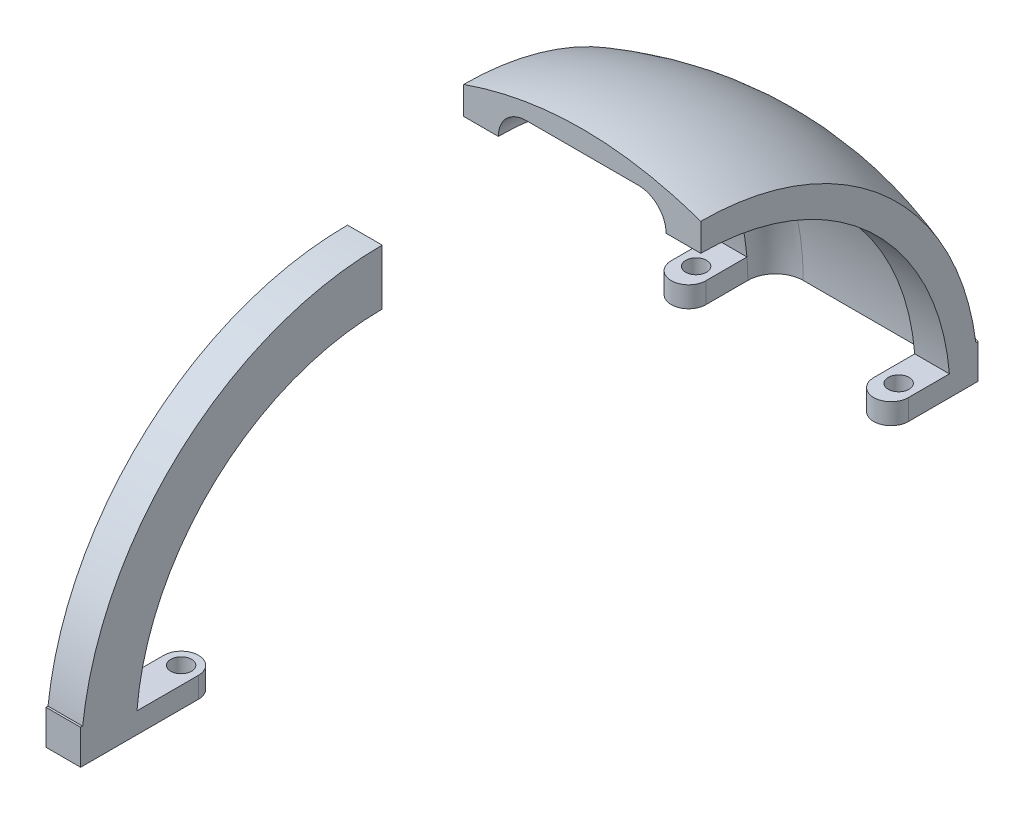
SolidWorks part; units mm, degrees
ref_plane "Front Plane" through (0, 0, 0) normal (0, 0, 1) x (1, 0, 0)
ref_plane "Top Plane" through (0, 0, 0) normal (0, 1, 0) x (1, 0, 0)
ref_plane "Right Plane" through (0, 0, 0) normal (1, 0, 0) x (0, 0, -1)
sketch "Sketch1" plane through (0, 0, 0) normal (0, 1, 0) x (1, 0, 0)
  line L0 (0, 55) -> (0, -55) construction
  line L1 (-55, 0) -> (55, 0) construction
  line L2 (-55, 20.7263) -> (-55, -21.0382) construction
  line L3 (-6.2, 54.0459) -> (10.01, 54.0459)
  line L4 (-15.2, 44) -> (-10.2, 44)
  line L5 (-15.2, 44) -> (-15.2, 54.0459)
  line L7 (-10.2, 44) -> (-10.2, 50.0459)
  line L12 (1.905, 54.0459) -> (1.905, 57.0459) construction
  line L13 (19.01, 44) -> (14.01, 44)
  line L14 (19.01, 44) -> (19.01, 54.0459)
  line L16 (14.01, 44) -> (14.01, 50.0459)
  line L17 (-10.2, 50.0459) -> (-15.2, 50.0459)
  line L22 (2.5, -41.91) -> (-2.5, -41.91)
  line L23 (2.5, -41.91) -> (2.5, -58.91)
  line L24 (2.5, -58.91) -> (-2.5, -58.91)
  line L25 (-2.5, -41.91) -> (-2.5, -58.91)
  line L26 (14.01, 50.0459) -> (19.01, 50.0459)
  line L27 (-2.5, -50.91) -> (2.5, -50.91)
  line L28 (-2.5, -15.41) -> (2.5, -15.41) construction
  circle A0 centre (0, 0) radius 55 construction
  circle A1 centre (0, -41.91) radius 1.5 construction
  circle A2 centre (16.5327, 45.0784) radius 1.5 construction
  circle A4 centre (0, -41.91) radius 1.5
  circle A8 centre (-12.7, 44) radius 2.5
  circle A9 centre (16.51, 44) radius 2.5
  circle A10 centre (0, -41.91) radius 2.5
  arc A11 (14.01, 50.0459) -> (10.01, 54.0459) centre (10.01, 50.0459) ccw
  arc A12 (-6.2, 54.0459) -> (-10.2, 50.0459) centre (-6.2, 50.0459) ccw
  circle A13 centre (0, 0) radius 50 construction
  circle A14 centre (-12.7049, 45.0912) radius 1.5 construction
  circle A15 centre (16.5327, 45.0784) radius 1.5
  circle A16 centre (-12.7049, 45.0912) radius 1.5
  spline S0 degree 2 poles (-15.2, 54.0459) (1.905, 60.0459) (19.01, 54.0459) knots 0 0 0 1 1 1
  dimension "D1" = 110
  dimension "D2" = 5
  dimension "D3" = 5
  dimension "D4" = 100
  dimension "D5" = 8
  dimension "D6" = 3
  dimension "D7" = 5
  dimension "D10" = 4
  dimension "D8" = 5
  dimension "D9" = 17
extrude "Boss-Extrude1" add sketch "Sketch1" along normal blind 3 contours A16 L4 A8 | A16 A8 L7 L17 L5 | A16 L4 A8 | A16 A8 L4 | S0 L5 L17 A12 L3 A11 L26 L14 | A15 L13 A9 | A15 L13 A9 | A15 A9 L13 | A15 A9 L14 L26 L16 | L27 L25 L24 L23 | A10 L25 L27 L23 | L22 A10 A4 | L22 A10 A4 region at (-9.2753, 0, -53.1212) region at (-12.6999, 0, -47.9735) region at (16.5098, 0, -47.9721) region at (-12.6997, 0, -42.8829) region at (-10.9002, 0, -44.8348) region at (14.7243, 0, -44.8518) region at (16.5085, 0, -42.8805) region at (-14.5064, 0, -44.8299) region at (18.3266, 0, -44.8292) region at (0, 0, 44.3541) region at (2, 0, 41.8541) region at (0, 0, 47.3696) region at (0, 0, 54.91)
extrude "Boss-Extrude2" add sketch "Sketch1<4>" along normal blind 5 contours S0 L5 L17 A12 L3 A11 L26 L14 | L27 L25 L24 L23 region at (-9.2753, 0, -53.1212) region at (0, 0, 54.91)
sketch "Sketch1<4>" plane through (0, 0, 0) normal (0, 1, 0) x (1, 0, 0) same geometry as "Sketch1"
sketch "Sketch2" plane through (0, 5, 0) normal (0, 1, 0) x (1, 0, 0)
  line L0 (14.01, 34.0459) -> (-10.2, 34.0459)
  line L5 (-15.2, 54.0459) -> (-15.2, 50.0459)
  line L6 (-15.2, 50.0459) -> (-10.2, 50.0459)
  line L7 (-6.2, 54.0459) -> (10.01, 54.0459)
  line L8 (14.01, 50.0459) -> (19.01, 50.0459)
  line L9 (19.01, 50.0459) -> (19.01, 54.0459)
  line L10 (-15.2, 54.0459) -> (-15.2, 50.0459)
  line L11 (-15.2, 50.0459) -> (-10.2, 50.0459)
  line L12 (-6.2, 54.0459) -> (10.01, 54.0459)
  line L13 (14.01, 50.0459) -> (19.01, 50.0459)
  line L14 (19.01, 50.0459) -> (19.01, 54.0459)
  arc A2 (-6.2, 54.0459) -> (-10.2, 50.0459) centre (-6.2, 50.0459) ccw
  arc A3 (14.01, 50.0459) -> (10.01, 54.0459) centre (10.01, 50.0459) ccw
  arc A4 (-6.2, 54.0459) -> (-10.2, 50.0459) centre (-6.2, 50.0459) ccw
  arc A5 (14.01, 50.0459) -> (10.01, 54.0459) centre (10.01, 50.0459) ccw
  parabola Q1 (19.01, 54.0459) -> (-15.2, 54.0459) focus (1.905, 32.6642) apex (1.905, 57.0459)
  parabola Q2 (19.01, 54.0459) -> (-15.2, 54.0459) focus (1.905, 32.6642) apex (1.905, 57.0459)
  dimension "D2" = 20
  dimension "D1" = 0
sketch "Sketch3" plane through (19.01, 0, 0) normal (1, 0, 0) x (0, 0, -1)
  line L6 (54.0459, 0) -> (54.0459, 5)
  line L7 (54.0459, 5) -> (50.0459, 5)
  line L8 (54.0459, 5) -> (50.0459, 5)
  line L9 (50.0459, 3) -> (44, 3)
  line L10 (44, 3) -> (44, 0)
  line L11 (44, 0) -> (54.0459, 0)
  line L12 (54.0459, 0) -> (54.0459, 5)
  line L15 (50.0459, 3) -> (44, 3)
  line L16 (44, 3) -> (44, 0)
  line L17 (44, 0) -> (54.0459, 0)
  line L18 (50.0459, 5) -> (50.0459, 3)
  line L19 (50.0459, 5) -> (50.0459, 3)
  circle A0 centre (-2, -5) radius 60 construction
  circle A1 centre (-2, -5) radius 50 construction
  point P7 (27.9809, 0)
  dimension "D1" = 0
  dimension "D3" = 100
  dimension "D4" = 120
  dimension "D2" = 46
  dimension "D5" = 5
sketch "Sketch6" plane through (0, 0, 0) normal (0, -1, 0) x (1, 0, 0)
  line L0 (-6.2, -14.0459) -> (10.01, -14.0459)
  line L1 (-15.2, -50.0459) -> (-10.2, -50.0459) construction
  line L2 (19.01, -50.0459) -> (14.01, -50.0459) construction
  line L3 (-15.2, -50.0459) -> (-10.2, -50.0459)
  line L4 (19.01, -50.0459) -> (14.01, -50.0459)
  line L5 (-15.2, -44) -> (-15.2, -54.0459)
  line L6 (19.01, -54.0459) -> (19.01, -44)
  line L7 (14.01, -44) -> (14.01, -50.0459)
  line L8 (10.01, -54.0459) -> (-6.2, -54.0459)
  line L9 (-10.2, -50.0459) -> (-10.2, -44)
  line L10 (-15.2, -44) -> (-15.2, -54.0459)
  line L11 (19.01, -54.0459) -> (19.01, -44)
  line L12 (14.01, -44) -> (14.01, -50.0459)
  line L13 (10.01, -54.0459) -> (-6.2, -54.0459)
  line L14 (-10.2, -50.0459) -> (-10.2, -44)
  arc A4 (19.01, -44) -> (14.01, -44) centre (16.51, -44) ccw
  arc A5 (10.01, -54.0459) -> (14.01, -50.0459) centre (10.01, -50.0459) ccw
  arc A6 (-10.2, -50.0459) -> (-6.2, -54.0459) centre (-6.2, -50.0459) ccw
  arc A7 (-10.2, -44) -> (-15.2, -44) centre (-12.7, -44) ccw
  arc A8 (19.01, -44) -> (14.01, -44) centre (16.51, -44) ccw
  arc A9 (10.01, -54.0459) -> (14.01, -50.0459) centre (10.01, -50.0459) ccw
  arc A10 (-10.2, -50.0459) -> (-6.2, -54.0459) centre (-6.2, -50.0459) ccw
  arc A11 (-10.2, -44) -> (-15.2, -44) centre (-12.7, -44) ccw
  parabola Q1 (-15.2, -54.0459) -> (19.01, -54.0459) focus (1.905, -32.6642) apex (1.905, -57.0459)
  parabola Q2 (-15.2, -54.0459) -> (19.01, -54.0459) focus (1.905, -32.6642) apex (1.905, -57.0459)
  dimension "D2" = 40
  dimension "D1" = 0
revolve "Revolve3" add sketch "Sketch6" angle 90 about L0 region at (-12.7, 0, -50.3951)
revolve "Revolve5" add sketch "Sketch1<6>" angle 90 about L28 region at (0, 0, 54.91) reverse direction yes
sketch "Sketch1<6>" plane through (0, 0, 0) normal (0, 1, 0) x (1, 0, 0) same geometry as "Sketch1"
sketch "Sketch7" plane through (0, 0, -14.0459) normal (0, 0, 1) x (1, 0, 0)
  line L4 (-2.5, 35.5) -> (2.5, 35.5)
  line L5 (19.01, 36) -> (19.01, 40)
  line L6 (-15.2, 40) -> (-15.2, 36)
  line L7 (-15.2, 36) -> (-10.2, 36)
  line L8 (-6.2, 40) -> (10.01, 40)
  line L9 (14.01, 36) -> (19.01, 36)
  line L10 (19.01, 36) -> (19.01, 40)
  line L11 (-15.2, 40) -> (-15.2, 36)
  line L12 (-15.2, 36) -> (-10.2, 36)
  line L13 (-6.2, 40) -> (10.01, 40)
  line L14 (14.01, 36) -> (19.01, 36)
  line L15 (-2.5, 43.5) -> (-2.5, 35.5)
  line L16 (2.5, 43.5) -> (-2.5, 43.5)
  line L17 (2.5, 35.5) -> (2.5, 43.5)
  line L18 (-2.5, 35.5) -> (2.5, 35.5)
  line L19 (-2.5, 43.5) -> (-2.5, 35.5)
  line L20 (2.5, 43.5) -> (-2.5, 43.5)
  line L21 (2.5, 35.5) -> (2.5, 43.5)
  arc A2 (-6.2, 40) -> (-10.2, 36) centre (-6.2, 36) ccw
  arc A3 (14.01, 36) -> (10.01, 40) centre (10.01, 36) ccw
  arc A4 (-6.2, 40) -> (-10.2, 36) centre (-6.2, 36) ccw
  arc A5 (14.01, 36) -> (10.01, 40) centre (10.01, 36) ccw
  parabola Q1 (19.01, 40) -> (-15.2, 40) focus (1.905, 18.6182) apex (1.905, 43)
  parabola Q2 (19.01, 40) -> (-15.2, 40) focus (1.905, 18.6182) apex (1.905, 43)
  dimension "D1" = 0
  dimension "D2" = 0
